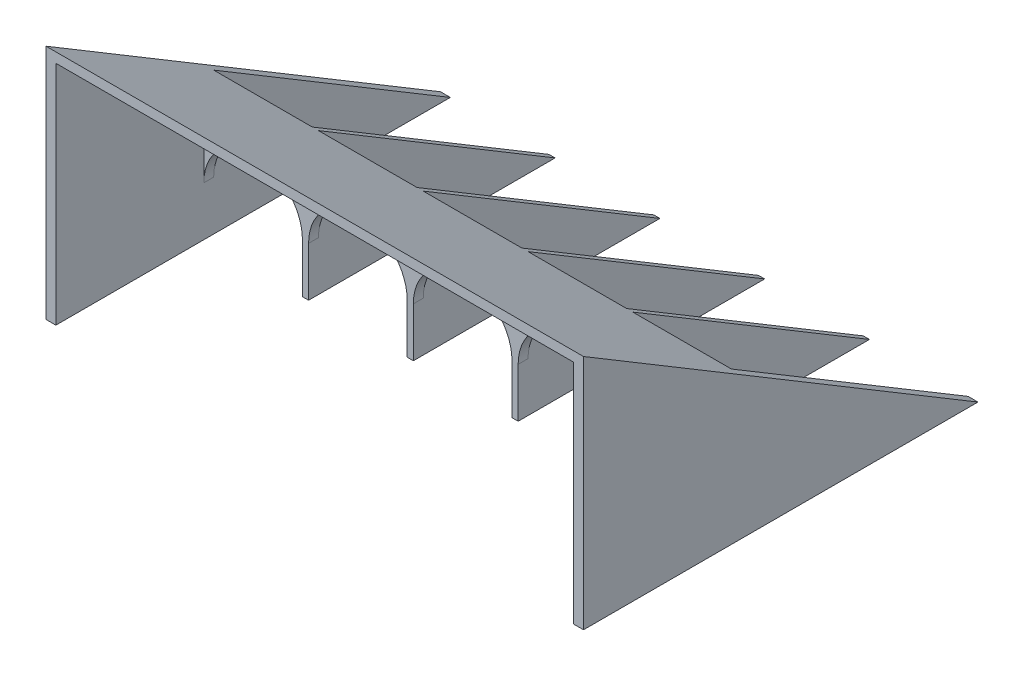
SolidWorks part; units mm, degrees
ref_plane "Alzado" through (0, 0, 0) normal (0, 0, 1) x (1, 0, 0)
ref_plane "Planta" through (0, 0, 0) normal (0, 1, 0) x (1, 0, 0)
ref_plane "Vista lateral" through (0, 0, 0) normal (1, 0, 0) x (0, 0, -1)
sketch "Croquis2" plane through (0, 0, 0) normal (1, 0, 0) x (0, 0, -1)
  line L0 (-60, 36) -> (-60, -60)
  line L1 (-60, -60) -> (100, -60)
  line L2 (100, -60) -> (-60, 36)
  dimension "D1" = 60
  dimension "D2" = 100
  dimension "D3" = 60
extrude "Saliente-Extruir1" add sketch "Croquis2" along normal blind 218
sketch3d "Croquis3D3"
  line L1 (4, -4, 0) -> (214, -4, 0)
  line L2 (4, -4, 0) -> (4, -60, 0)
  line L3 (4, -60, 0) -> (214, -60, 0)
  line L4 (214, -4, 0) -> (214, -60, 0)
  point P4 (0, -60, 0)
  point P5 (0, 36, 0)
  point P6 (218, -60, 0)
  dimension "D1" = 0
  dimension "D2" = 4
  dimension "D3" = 4
  dimension "D4" = 56
sketch "Croquis3" plane through (0, 0, 60) normal (0, 0, 1) x (1, 0, 0)
  line L0 (0, 36) -> (0, -60) construction
  line L1 (4, 32) -> (214, 32)
  line L2 (4, 32) -> (4, -60)
  line L3 (4, -60) -> (214, -60)
  line L4 (214, 32) -> (214, -60)
  line L5 (4, -60) -> (214, -60) construction
  line L6 (218, 36) -> (218, -60) construction
  line L7 (218, 36) -> (0, 36) construction
  dimension "D1" = 4
  dimension "D2" = 0
  dimension "D3" = 4
  dimension "D4" = 4
loft "Cortar-Recubrir1" cut profiles "Croquis3", "Croquis3D3"
sketch "Croquis4" plane through (0, -60, 0) normal (0, -1, 0) x (1, 0, 0)
  line L0 (218, -100) -> (0, -100) construction
  line L1 (214, 0) -> (4, 0) construction
  line L2 (4, 0) -> (214, 0) construction
  line L3 (4, -4) -> (44, -4)
  line L4 (4, -4) -> (4, -100)
  line L5 (4, -100) -> (44, -100)
  line L6 (44, -4) -> (44, -100)
  line L8 (46.5, -4) -> (86.5, -4)
  line L9 (46.5, -4) -> (46.5, -100)
  line L10 (46.5, -100) -> (86.5, -100)
  line L11 (86.5, -4) -> (86.5, -100)
  line L12 (89, -4) -> (129, -4)
  line L13 (89, -4) -> (89, -100)
  line L14 (89, -100) -> (129, -100)
  line L15 (129, -4) -> (129, -100)
  line L16 (131.5, -4) -> (171.5, -4)
  line L17 (131.5, -4) -> (131.5, -100)
  line L18 (131.5, -100) -> (171.5, -100)
  line L19 (171.5, -4) -> (171.5, -100)
  line L20 (174, -4) -> (214, -4)
  line L21 (174, -4) -> (174, -100)
  line L22 (174, -100) -> (214, -100)
  line L23 (214, -4) -> (214, -100)
  point P0 (44, 0)
  point P1 (214, 0)
  point P2 (4, 0)
  point P6 (174, 0)
  point P8 (171.5, 0)
  point P11 (46.5, 0)
  point P12 (86.5, 0)
  point P13 (131.5, 0)
  point P14 (89, 0)
  point P15 (129, 0)
  dimension "D1" = 40
  dimension "D2" = 40
  dimension "D3" = 2.5
  dimension "D4" = 2.5
  dimension "D5" = 40
  dimension "D6" = 40
  dimension "D7" = 2.5
  dimension "D8" = 2.5
  dimension "D9" = 40
  dimension "D10" = 4
  dimension "D11" = 4
  dimension "D12" = 4
  dimension "D13" = 4
  dimension "D14" = 4
extrude "Cortar-Extruir1" cut sketch "Croquis4" against normal blind 60
sketch "Croquis5" plane through (0, 0, -4) normal (0, 0, -1) x (-1, 0, 0)
  line L0 (-194, -60) -> (-174, -60)
  line L1 (-214, -60) -> (-174, -60) construction
  line L2 (-174, -60) -> (-174, -20)
  line L3 (-174, -20) -> (-214, -20)
  line L4 (-214, -20) -> (-214, -60)
  line L5 (-214, -60) -> (-194, -60)
  line L6 (-151.5, -60) -> (-131.5, -60)
  line L7 (-171.5, -60) -> (-131.5, -60) construction
  line L8 (-131.5, -60) -> (-131.5, -20)
  line L9 (-131.5, -20) -> (-171.5, -20)
  line L10 (-171.5, -20) -> (-171.5, -60)
  line L11 (-171.5, -60) -> (-151.5, -60)
  line L12 (-109, -60) -> (-89, -60)
  line L13 (-129, -60) -> (-89, -60) construction
  line L14 (-89, -60) -> (-89, -20)
  line L15 (-89, -20) -> (-129, -20)
  line L16 (-129, -20) -> (-129, -60)
  line L17 (-129, -60) -> (-109, -60)
  line L18 (-66.5, -60) -> (-46.5, -60)
  line L19 (-86.5, -60) -> (-46.5, -60) construction
  line L20 (-46.5, -60) -> (-46.5, -20)
  line L21 (-46.5, -20) -> (-86.5, -20)
  line L22 (-86.5, -20) -> (-86.5, -60)
  line L23 (-86.5, -60) -> (-66.5, -60)
  line L24 (-24, -60) -> (-4, -60)
  line L25 (-44, -60) -> (-4, -60) construction
  line L26 (-4, -60) -> (-4, -20)
  line L27 (-4, -20) -> (-44, -20)
  line L28 (-44, -20) -> (-44, -60)
  line L29 (-44, -60) -> (-24, -60)
  dimension "D1" = 20
  dimension "D2" = 20
  dimension "D3" = 40
  dimension "D4" = 20
  dimension "D5" = 20
  dimension "D6" = 40
  dimension "D7" = 20
  dimension "D8" = 20
  dimension "D9" = 20
  dimension "D10" = 20
  dimension "D11" = 20
  dimension "D12" = 20
  dimension "D13" = 40
  dimension "D14" = 40
  dimension "D15" = 40
extrude "Cortar-Extruir2" cut sketch "Croquis5" against normal blind 4
fillet "Redondeo1" radius 20 10 edges at (44, -20, -2) (46.5, -20, -2) (86.5, -20, -2) (89, -20, -2) (129, -20, -2) (131.5, -20, -2) (171.5, -20, -2) (174, -20, -2)
